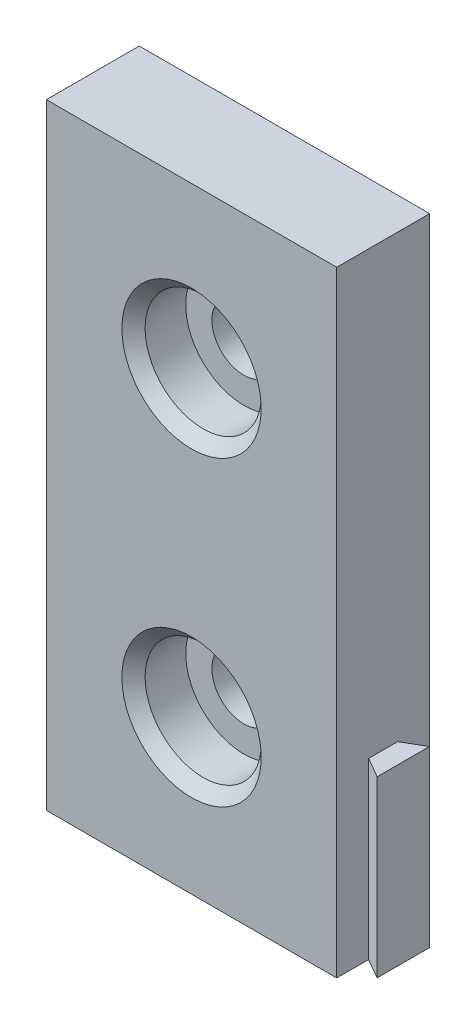
SolidWorks part; units mm, degrees
ref_plane "Front Plane" through (0, 0, 0) normal (0, 0, 1) x (1, 0, 0)
ref_plane "Top Plane" through (0, 0, 0) normal (0, 1, 0) x (1, 0, 0)
ref_plane "Right Plane" through (0, 0, 0) normal (1, 0, 0) x (0, 0, -1)
sketch "Sketch2" plane through (0, 0, 0) normal (0, 0, 1) x (1, 0, 0)
  line L0 (12.5, 53) -> (12.5, -45.5968) construction
  line L1 (0, 0) -> (25, 0)
  line L2 (0, 0) -> (0, 53)
  line L3 (0, 53) -> (25, 53)
  line L4 (25, 0) -> (25, 53)
  line L5 (0, 26.2) -> (42.3407, 26.2) construction
  circle A0 centre (12.5, 39.2) radius 2.75
  circle A1 centre (12.5, 13.2) radius 2.75
  dimension "D3" = 5.5
  dimension "D4" = 13
  dimension "D1" = 53
  dimension "D2" = 25
  dimension "D5" = 13
  dimension "D6" = 26.2
extrude "Boss-Extrude1" add sketch "Sketch2" along normal blind 8
sketch "Sketch3" plane through (0, 0, 0) normal (0, -1, 0) x (1, 0, 0)
  line L0 (25, 2.75) -> (26.7321, 1.75)
  line L1 (26.7321, 1.75) -> (26.7321, 6.25)
  line L2 (26.7321, 6.25) -> (25, 5.25)
  line L3 (25, 8) -> (25, 0) construction
  line L4 (25, 2.75) -> (25, 5.25)
  point P11 (25, 4)
  point P12 (25, 4)
  dimension "D1" = 60
  dimension "D2" = 60
  dimension "D3" = 4.5
  dimension "D4" = 2.5
extrude "Boss-Extrude2" add sketch "Sketch3" against normal blind 15
sketch "Sketch4" plane through (0, 0, 8) normal (0, 0, 1) x (1, 0, 0)
  circle A0 centre (12.5, 39.2) radius 5
  circle A1 centre (12.5, 13.2) radius 5
  dimension "D1" = 10
extrude "Cut-Extrude1" cut sketch "Sketch4" against normal blind 4.5
chamfer "Chamfer1" distance 1 angle 45 2 edges at (17.5, 39.2, 8) (17.5, 13.2, 8)
